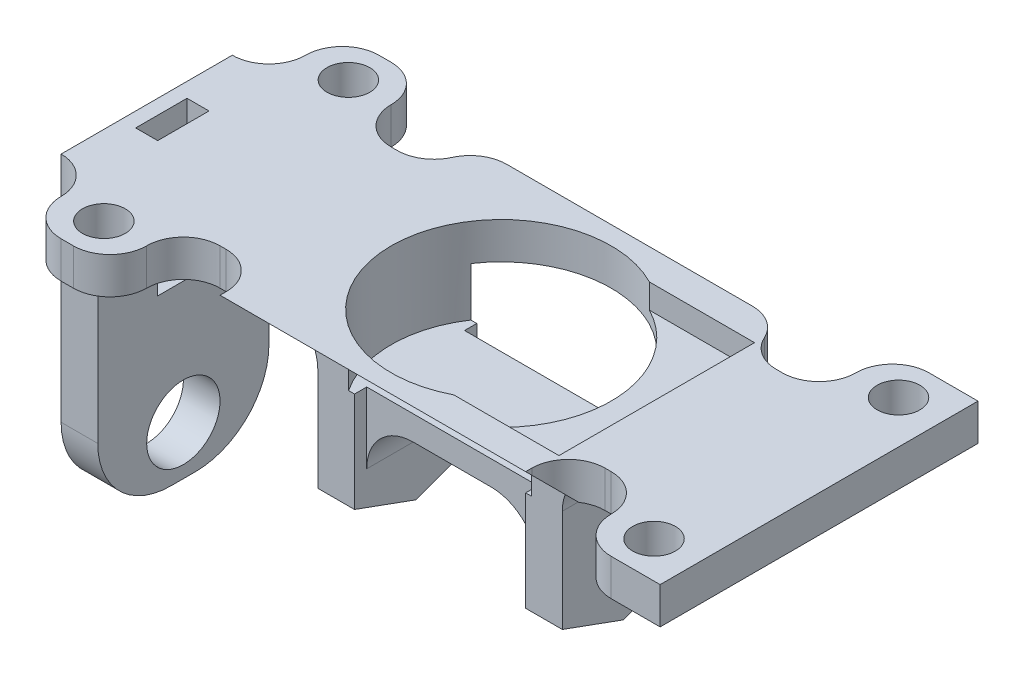
SolidWorks part; units mm, degrees
ref_plane "Front Plane" through (0, 0, 0) normal (0, 0, 1) x (1, 0, 0)
ref_plane "Top Plane" through (0, 0, 0) normal (0, 1, 0) x (1, 0, 0)
ref_plane "Right Plane" through (0, 0, 0) normal (1, 0, 0) x (0, 0, -1)
sketch "Sketch1" plane through (0, 0, 0) normal (0, 1, 0) x (1, 0, 0)
  line L1 (-1.5, 7) -> (1.5, 7)
  line L2 (-1.5, 7) -> (-1.5, -7)
  line L3 (-1.5, -7) -> (1.5, -7)
  line L4 (1.5, 7) -> (1.5, -7)
  line L5 (-1.5, 7) -> (1.5, -7) construction
  line L6 (-1.5, -7) -> (1.5, 7) construction
  point P0 (0, 0)
  dimension "D1" = 14
  dimension "D2" = 3
extrude "Boss-Extrude1" add sketch "Sketch1" along normal blind 25
sketch "Sketch2" plane through (-1.5, 0, 0) normal (-1, 0, 0) x (0, 0, 1)
  line L0 (-7, 0) -> (7, 0) construction
  circle A0 centre (0, 4) radius 3
  point P5 (0, 0)
  dimension "D1" = 6
  dimension "D2" = 4
extrude "Cut-Extrude1" cut sketch "Sketch2" against normal through all
sketch "Sketch3" plane through (1.5, 0, 0) normal (1, 0, 0) x (0, 0, -1)
  line L0 (7, 25) -> (7, 0) construction
  line L1 (-7, 25) -> (7, 25)
  line L2 (-7, 25) -> (-7, 22)
  line L3 (-7, 22) -> (7, 22)
  line L4 (7, 25) -> (7, 22)
  dimension "D1" = 3
extrude "Boss-Extrude2" add sketch "Sketch3" along normal blind 52
sketch "Sketch4" plane through (0, 22, 0) normal (0, -1, 0) x (1, 0, 0)
  line L0 (53.5, 7) -> (53.5, -7) construction
  line L1 (37.5, 5) -> (34.5, 5)
  line L2 (37.5, 5) -> (37.5, -5)
  line L3 (37.5, -5) -> (34.5, -5)
  line L4 (17.5, 5) -> (17.5, -5)
  line L5 (37.5, 5) -> (17.5, -5) construction
  line L6 (37.5, -5) -> (17.5, 5) construction
  line L7 (53.5, 7) -> (1.5, 7) construction
  line L8 (20.5, -5) -> (17.5, -5)
  line L10 (20.5, -5) -> (20.5, 5)
  line L12 (34.5, -5) -> (34.5, 5)
  line L13 (20.5, 5) -> (17.5, 5)
  point P0 (27.5, 0)
  point P8 (53.5, 0)
  point P11 (27.5, 7)
  dimension "D1" = 10
  dimension "D2" = 20
  dimension "D3" = 3
  dimension "D4" = 3
extrude "Boss-Extrude3" add sketch "Sketch4" along normal blind 14
chamfer "Chamfer1" distance 5 angle 20 4 edges at (36, 8, -5) (36, 8, 5) (19, 8, 5) (19, 8, -5) first distance on face at (36, 8, 0) first distance on face at (19, 8, 0)
ref_plane "Plane1" through (27.5, 0, 0) normal (-1, 0, 0) x (0, 0, 1)
sketch "Sketch6" plane through (0, 0, -7) normal (0, 0, -1) x (-1, 0, 0)
  line L0 (-53.5, 25) -> (1.5, 25) construction
  line L1 (-40, 25) -> (-15, 25)
  line L2 (-40, 25) -> (-40, 22)
  line L3 (-40, 22) -> (-15, 22)
  line L4 (-15, 25) -> (-15, 22)
  line L5 (-53.5, 22) -> (-1.5, 22) construction
  point P8 (-27.5, 22)
  point P9 (-27.5, 22)
  dimension "D1" = 25
extrude "Boss-Extrude5" add sketch "Sketch6" along normal blind 3.5
sketch "Sketch5" plane through (0, 0, 7) normal (0, 0, 1) x (1, 0, 0)
  line L0 (-1.5, 25) -> (53.5, 25) construction
  line L1 (1.5, 25) -> (8.5, 25)
  line L2 (1.5, 25) -> (1.5, 22)
  line L3 (1.5, 22) -> (8.5, 22)
  line L4 (8.5, 25) -> (8.5, 22)
  line L5 (53.5, 22) -> (1.5, 22) construction
  line L6 (27.5, 5.5) -> (27.5, -5.5) construction
  line L7 (53.5, 22) -> (46.5, 22)
  line L8 (46.5, 25) -> (46.5, 22)
  line L9 (53.5, 25) -> (46.5, 25)
  line L10 (53.5, 25) -> (53.5, 22)
  point P14 (5, 22)
  dimension "D1" = 7
  dimension "D2" = 22.5
extrude "Boss-Extrude4" add sketch "Sketch5" along normal blind 6
mirror "Mirror1" about plane through (0, 0, 0) normal (0, 0, 1) of "Boss-Extrude4", "Boss-Extrude5"
sketch "Sketch7" plane through (0, 25, 0) normal (0, 1, 0) x (1, 0, 0)
  line L0 (27.5, 5.5) -> (27.5, -5.5) construction
  circle A0 centre (27.5, 0) radius 9
  dimension "D1" = 18
extrude "Cut-Extrude2" cut sketch "Sketch7" against normal blind 7
chamfer "Chamfer2" distance 3 angle 45 1 edges at (27.5, 22, 10.5)
sketch "Sketch8" plane through (20.5, 0, 0) normal (1, 0, 0) x (0, 0, -1)
  line L0 (-5, 18) -> (5, 18) construction
  line L1 (4, 18) -> (-4, 18)
  line L2 (4, 18) -> (4, 16)
  line L3 (4, 16) -> (-4, 16)
  line L4 (-4, 18) -> (-4, 16)
  point P6 (0, 18)
  point P7 (0, 18)
  dimension "D1" = 2
  dimension "D2" = 8
extrude "Boss-Extrude6" add sketch "Sketch8" along normal up to vertex (14 mm away) up to point (34.5, 18, 5)
sketch "Sketch9" plane through (0, 25, 0) normal (0, 1, 0) x (1, 0, 0)
  line L1 (40.2231, 8) -> (31.6231, 8)
  line L2 (40.2231, 8) -> (40.2231, -8)
  line L3 (40.2231, -8) -> (31.6231, -8)
  line L4 (31.6231, 8) -> (31.6231, -8)
  circle A0 centre (27.5, 0) radius 9 construction
  dimension "D1" = 16
  dimension "D2" = 8.6
extrude "Cut-Extrude3" cut sketch "Sketch9" against normal blind 2
sketch "Sketch10" plane through (0, 25, 0) normal (0, 1, 0) x (1, 0, 0)
  line L0 (8.5, -13) -> (1.5, -13) construction
  line L1 (1.5, -13) -> (1.5, -7) construction
  line L2 (1.5, 13) -> (1.5, 7) construction
  line L3 (8.5, 13) -> (1.5, 13) construction
  line L4 (53.5, -13) -> (46.5, -13) construction
  circle A0 centre (5, -10) radius 1.75
  circle A1 centre (50, -10) radius 1.75
  circle A2 centre (50, 10) radius 1.75
  circle A3 centre (5, 10) radius 1.75
  point P5 (5, -13)
  point P8 (1.5, -10)
  point P18 (1.5, 10)
  point P23 (5, 13)
  point P27 (50, -13)
  dimension "D1" = 3.5
  dimension "D2" = 2
  dimension "D3" = 2
extrude "Cut-Extrude4" cut sketch "Sketch10" against normal up to next
sketch "Sketch11" plane through (0, 25, 0) normal (0, 1, 0) x (1, 0, 0)
  line L0 (1.5, -7) -> (1.5, 7) construction
  line L1 (-0.3, 2.1) -> (1.5, 2.1)
  line L2 (-0.3, 2.1) -> (-0.3, -2.1)
  line L3 (-0.3, -2.1) -> (1.5, -2.1)
  line L4 (1.5, 2.1) -> (1.5, -2.1)
  line L5 (-0.3, 2.1) -> (1.5, -2.1) construction
  line L6 (-0.3, -2.1) -> (1.5, 2.1) construction
  point P0 (0.6, 0)
  dimension "D1" = 1.8
  dimension "D2" = 0
  dimension "D3" = 4.2
extrude "Cut-Extrude5" cut sketch "Sketch11" against normal blind 11
fillet "Fillet1" radius 3 10 edges at (46.5, 23.5, 7) (40, 22.5, 7) (15, 23.5, 7) (8.5, 23.5, 7) (1.5, 23.5, 7) (1.5, 23.5, -7) (8.5, 23.5, -7) (15, 23.5, -7) (46.5, 23.5, -7) (40, 22.5, -7)
fillet "Fillet2" radius 3 8 edges at (46.5, 23.5, 13) (46.5, 23.5, -13) (40, 23.5, -10.5) (15, 23.5, -10.5) (8.5, 23.5, 13) (1.5, 23.5, 13) (1.5, 23.5, -13) (8.5, 23.5, -13)
fillet "Fillet3" radius 3.8 6 edges at (37.5, 22, 0) (20.5, 16, 0) (34.5, 16, 0) (17.5, 22, 0) (1.5, 22, 4.55) (1.5, 22, -4.55)
fillet "Fillet4" radius 6 2 edges at (0, 0, -7) (0, 0, 7)
equation "\"D4@Sketch4\"=\"D3@Sketch4\""
